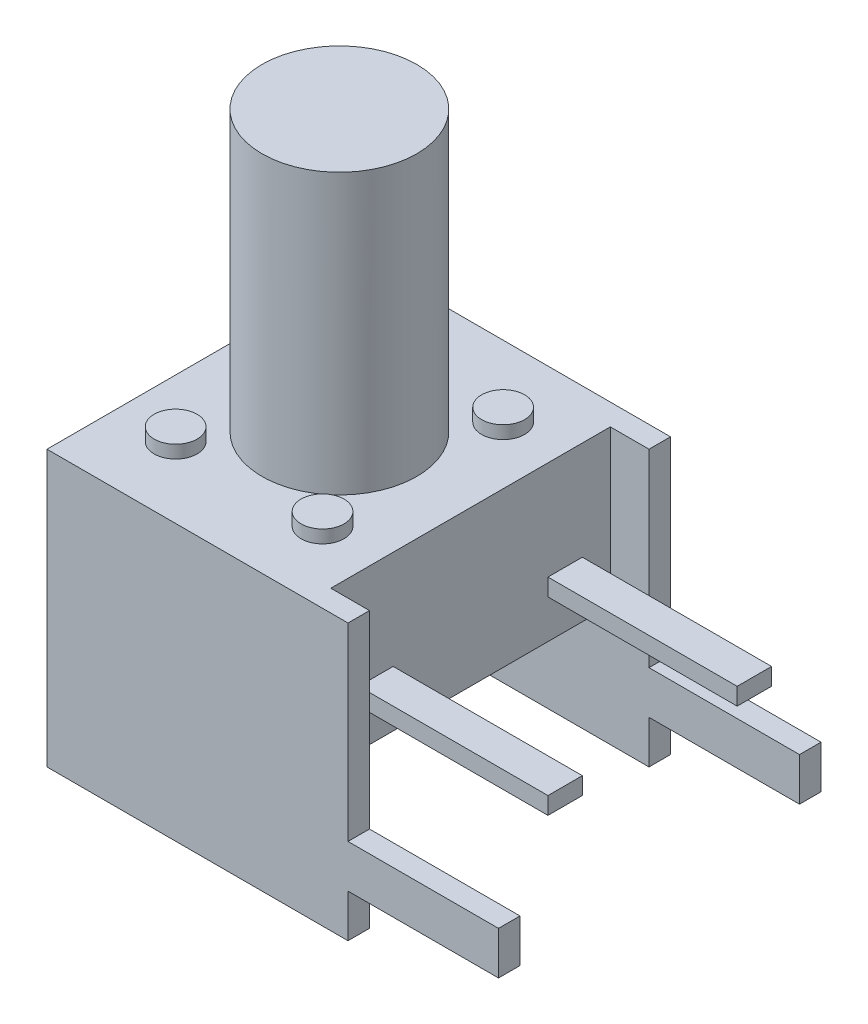
SolidWorks part; units mm, degrees
ref_plane "前视基准面" through (0, 0, 0) normal (0, 0, 1) x (1, 0, 0)
ref_plane "上视基准面" through (0, 0, 0) normal (0, 1, 0) x (1, 0, 0)
ref_plane "右视基准面" through (0, 0, 0) normal (1, 0, 0) x (0, 0, -1)
other "Configuration Table"
sketch "草图1" plane through (0, 0, 0) normal (0, 1, 0) x (1, 0, 0)
  line L1 (-3.05, -3.75) -> (3.05, -3.75)
  line L2 (-3.05, -3.75) -> (-3.05, 3.75)
  line L3 (-3.05, 3.75) -> (3.05, 3.75)
  line L4 (3.05, -3.75) -> (3.05, 3.75)
  line L5 (-3.05, -3.75) -> (3.05, 3.75) construction
  line L6 (-3.05, 3.75) -> (3.05, -3.75) construction
  circle A0 centre (0, 0) radius 1.8
  circle A1 centre (-1.708, 2.1) radius 0.5
  circle A2 centre (-1.708, -2.1) radius 0.5
  circle A3 centre (1.708, -2.1) radius 0.5
  circle A4 centre (1.708, 2.1) radius 0.5
  point P0 (0, 0)
  dimension "D3" = 3.6
  dimension "D5" = 1
  dimension "D1" = 7.5
  dimension "D2" = 6.1
  dimension "D4" = 4.2
extrude "凸台-拉伸1" add sketch "草图1" along normal blind 3.6 contours L3 L4 L1 L2
extrude "凸台-拉伸2" add sketch "草图1<3>" along normal blind 10.1 contours A0
sketch "草图1<3>" plane through (0, 0, 0) normal (0, 1, 0) x (1, 0, 0) same geometry as "草图1"
extrude "凸台-拉伸3" add sketch "草图1<4>" along normal blind 0.3 from surface contours A1 | A2 | A4 | A3 starting at face at (0, 3.6, -1.8)
sketch "草图1<4>" plane through (0, 0, 0) normal (0, 1, 0) x (1, 0, 0) same geometry as "草图1"
sketch "草图2" plane through (3.05, 0, 0) normal (1, 0, 0) x (0, 0, -1)
  line L0 (-1.8, 1.1) -> (1.8, 1.1)
  line L1 (-2.6, 0.9) -> (-1.8, 0.9)
  line L2 (-2.6, 0.9) -> (-2.6, 1.3)
  line L3 (-2.6, 1.3) -> (-1.8, 1.3)
  line L4 (-1.8, 0.9) -> (-1.8, 1.3)
  line L5 (1.8, 0.9) -> (2.6, 0.9)
  line L6 (1.8, 0.9) -> (1.8, 1.3)
  line L7 (1.8, 1.3) -> (2.6, 1.3)
  line L8 (2.6, 0.9) -> (2.6, 1.3)
  line L9 (0, 0) -> (0, 3.6)
  line L10 (-3.75, 3.6) -> (3.75, 3.6) construction
  line L12 (-3.75, 0) -> (3.75, 0) construction
  point P15 (0, 1.1)
  dimension "D1" = 5.2
  dimension "D2" = 0.8
  dimension "D3" = 0.4
  dimension "D4" = 1.3
extrude "凸台-拉伸4" add sketch "草图2" along normal blind 4.4 contours L3 L4 L1 L2 | L7 L8 L5 L6
sketch "草图4" plane through (3.05, 0, 0) normal (1, 0, 0) x (0, 0, -1)
  line L0 (3.75, 3.6) -> (3.75, 0) construction
  line L1 (-3.75, 3.6) -> (-3.25, 3.6)
  line L2 (-3.75, 3.6) -> (-3.75, -2.8)
  line L3 (-3.75, -2.8) -> (-3.25, -2.8)
  line L4 (-3.25, 3.6) -> (-3.25, -2.8)
  line L5 (3.75, 3.6) -> (3.25, 3.6)
  line L6 (3.75, 3.6) -> (3.75, -2.8)
  line L7 (3.75, -2.8) -> (3.25, -2.8)
  line L8 (3.25, 3.6) -> (3.25, -2.8)
  line L9 (-3.75, 3.6) -> (3.75, 3.6) construction
  line L11 (3.25, -0.8) -> (3.75, -0.8)
  line L12 (3.25, -0.8) -> (3.25, -1.8)
  line L13 (3.25, -1.8) -> (3.75, -1.8)
  line L14 (3.75, -0.8) -> (3.75, -1.8)
  line L15 (-3.25, -0.8) -> (-3.75, -0.8)
  line L16 (-3.25, -0.8) -> (-3.25, -1.8)
  line L17 (-3.25, -1.8) -> (-3.75, -1.8)
  line L18 (-3.75, -0.8) -> (-3.75, -1.8)
  dimension "D1" = 6.4
  dimension "D2" = 0.5
  dimension "D3" = 1
  dimension "D4" = 2
extrude "凸台-拉伸5" add sketch "草图4" along normal blind 7 from surface contours L6 L7 L8 L5 | L4 L3 L2 L1 starting at face at (-3.05, 1.8, 0)
extrude "凸台-拉伸6" add sketch "草图4<3>" along normal up to surface (4.4 mm away) contours L17 L18 L15 L16 | L13 L14 L11 L12 up to face at (7.45, 1.1, 2.2)
sketch "草图4<3>" plane through (3.05, 0, 0) normal (1, 0, 0) x (0, 0, -1) same geometry as "草图4"
